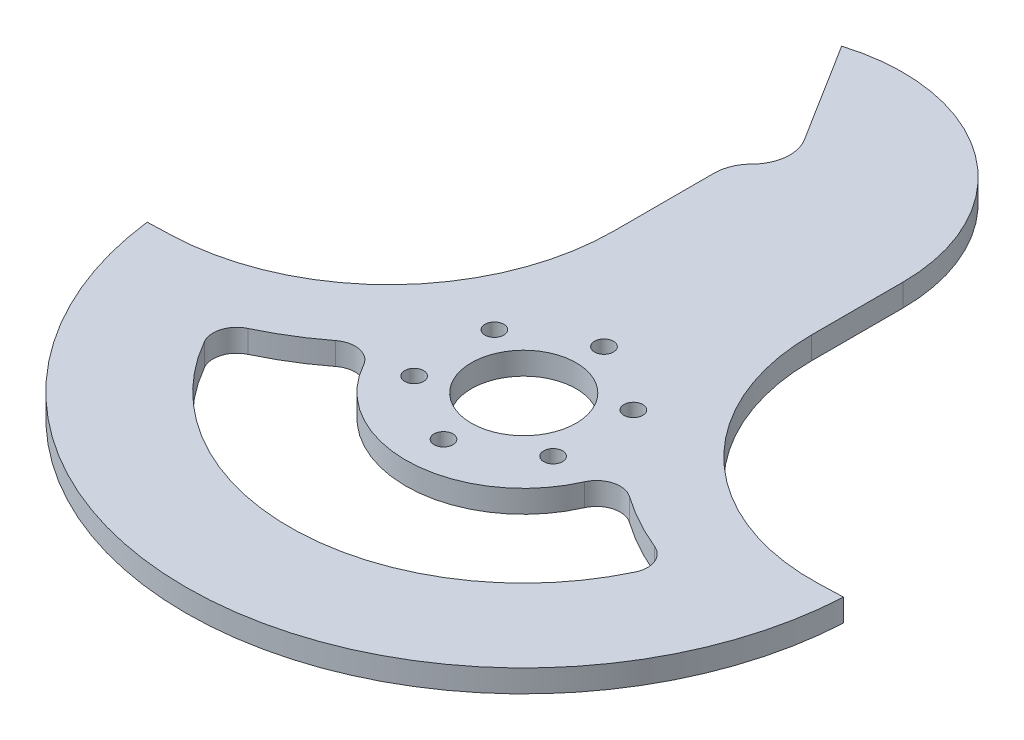
SolidWorks part; units mm, degrees
ref_plane "Front Plane" through (0, 0, 0) normal (0, 0, 1) x (1, 0, 0)
ref_plane "Top Plane" through (0, 0, 0) normal (0, 1, 0) x (1, 0, 0)
ref_plane "Right Plane" through (0, 0, 0) normal (1, 0, 0) x (0, 0, -1)
other "Center of Mass"
sketch "Sketch1" plane through (0, 0, 0) normal (0, 1, 0) x (1, 0, 0)
  line L0 (0, 0) -> (-23040.0357, 36803.9862) construction
  line L1 (0, -1000) -> (0, 49000) construction
  line L2 (-29.7853, 97.136) -> (-16.5198, 75.9457)
  line L3 (18.7342, 112.0138) -> (41531.855, 12841.4067) construction
  line L4 (-20, 60.3286) -> (20, 60.3286) construction
  line L5 (-20, 60.3286) -> (-20, 39.1549)
  line L6 (20, 60.3286) -> (20, 40.9875)
  line L7 (0, 0) -> (-71.0663, -8.7258) construction
  line L8 (0, 0) -> (71.5019, -3.7473) construction
  line L9 (-71.0663, -8.7258) -> (71.5019, -3.7473) construction
  line L10 (-71.0663, -8.7258) -> (-66.0694, -8.5513)
  line L11 (71.5019, -3.7473) -> (66.5049, -3.9218)
  line L12 (-28.8426, 54.8122) -> (35326.4965, 35410.1512) construction
  circle A0 centre (0, 0) radius 101.6 construction
  arc A1 (-16.5198, 75.9457) -> (-17.6481, 66.0067) centre (-23.3262, 71.6848) cw
  arc A2 (-17.6481, 66.0067) -> (-20, 60.3286) centre (-11.97, 60.3286) ccw
  arc A3 (-29.7853, 97.136) -> (20, 60.3286) centre (-18.4989, 60.3286) cw
  circle A4 centre (0, 0) radius 71.6 construction
  arc A5 (-71.0663, -8.7258) -> (71.5019, -3.7473) centre (0, 0) ccw
  arc A6 (-66.0694, -8.5513) -> (-20, 39.1549) centre (-67.7353, 39.1549) ccw
  arc A7 (20, 40.9875) -> (66.5049, -3.9218) centre (64.9367, 40.9875) ccw
  circle A8 centre (0, 0) radius 30.5026 construction
  point P9 (0, 60.3286)
  point P20 (0, -71.6)
  point P21 (0, -101.6)
  point P31 (2.4988, -71.5564)
  point P34 (-15.2961, 71.6848)
  dimension "D1" = 203.2
  dimension "D2" = 75
  dimension "D3" = 25
  dimension "D4" = 40
  dimension "D5" = 30
  dimension "D6" = 92
  dimension "D7" = 170
  dimension "D8" = 5
  dimension "D9" = 45
extrude "Boss-Extrude1" add sketch "Sketch1" along normal blind 4.7625
sketch "Sketch6" plane through (0, 4.7625, 0) normal (0, 1, 0) x (1, 0, 0)
  line L0 (-41.0794, -17.6358) -> (-47.4528, -4.0572) construction
  line L1 (29.2213, -7.1458) -> (38.1596, 4.9002) construction
  arc A0 (-45.5884, -19.5412) -> (46.8909, -16.168) centre (0, 0) ccw
  arc A1 (-16.623, 2.7783) -> (-45.5884, -19.5412) centre (-67.7353, 39.1549) cw
  arc A2 (14.252, 8.9958) -> (46.8909, -16.168) centre (64.9367, 40.9875) ccw
  arc A3 (-16.623, 2.7783) -> (14.252, 8.9958) centre (0, 0) ccw
  arc A4 (-66.0694, -8.5513) -> (-20, 39.1549) centre (-67.7353, 39.1549) ccw construction
  arc A5 (-71.0663, -8.7258) -> (71.5019, -3.7473) centre (0, 0) ccw construction
  arc A6 (20, 40.9875) -> (66.5049, -3.9218) centre (64.9367, 40.9875) ccw construction
  circle A7 centre (0, 0) radius 30.5026 construction
  point P23 (0, -49.6)
  dimension "D1" = 22
  dimension "D2" = 15
extrude "Cut-Extrude2" cut sketch "Sketch6" against normal through all
fillet "Fillet6" radius 5 2 edges at (46.8909, 2.3813, 16.168) (-45.5884, 2.3813, 19.5412)
sketch "Sketch7" plane through (0, 4.7625, 0) normal (0, 1, 0) x (1, 0, 0)
  circle A0 centre (0, 0) radius 25
  dimension "D1" = 50
extrude "Boss-Extrude5" add sketch "Sketch7" against normal up to surface (4.7625 mm away) up to face at (0.9289, 0, 19.6333)
fillet "Fillet7" radius 5 2 edges at (24.7558, 2.3813, 3.486) (-24.2527, 2.3813, 6.0666)
sketch "Sketch8" plane through (0, 4.7625, 0) normal (0, 1, 0) x (1, 0, 0)
  circle A0 centre (0.1682, -0.1726) radius 11.1
  point P2 (0, 0)
  dimension "D1" = 22.2
extrude "Cut-Extrude3" cut sketch "Sketch8" against normal through all
sketch "Sketch10" plane through (0, 4.7625, 0) normal (0, 1, 0) x (1, 0, 0)
  circle A0 centre (0.1682, -17.1726) radius 7.8266 construction
  circle A1 centre (0, 0) radius 25 construction
  circle A3 centre (0.1682, -17.1726) radius 2
  circle A4 centre (-14.5543, -8.6726) radius 2
  circle A5 centre (-14.5543, 8.3274) radius 2
  circle A6 centre (0.1682, 16.8274) radius 2
  circle A7 centre (14.8906, 8.3274) radius 2
  circle A8 centre (14.8906, -8.6726) radius 2
  point P21 (0.1682, -0.1726)
  dimension "D1" = 4
  dimension "D3" = 34
  dimension "D2" = 6
extrude "Cut-Extrude4" cut sketch "Sketch10" against normal through all
sketch "Sketch11" plane through (0, 0, 0) normal (0, 1, 0) x (1, 0, 0)
  circle A0 centre (0.1682, -0.1726) radius 101.8143 construction
  circle A1 centre (0.1682, -0.1726) radius 11.1 construction
  circle A2 centre (0.1682, -0.1726) radius 71.7461 construction
ref_axis "Axis1" through (0.1682, 0, 0.1726) along (0, 1, 0)
